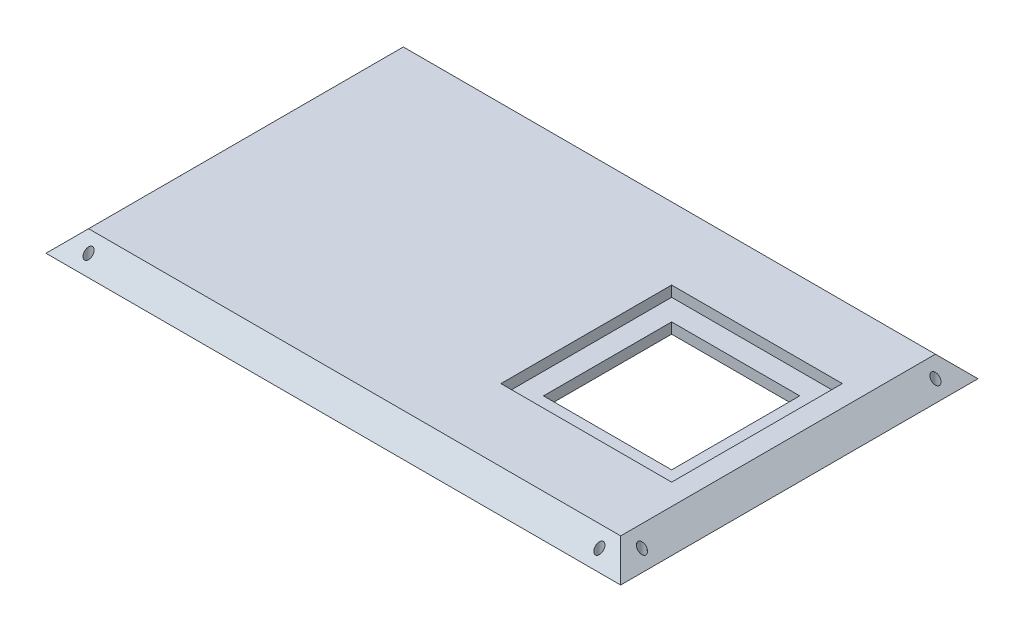
SolidWorks part; units mm, degrees
note: The reader was unsure of these and kept them because the rebuilt part matched: shared geometry of "Эскиз6<3>".
ref_plane "Спереди" through (0, 0, 0) normal (0, 0, 1) x (1, 0, 0)
ref_plane "Сверху" through (0, 0, 0) normal (0, 1, 0) x (1, 0, 0)
ref_plane "Справа" through (0, 0, 0) normal (1, 0, 0) x (0, 0, -1)
sketch "Эскиз1" plane through (0, 0, 0) normal (0, 1, 0) x (1, 0, 0)
  line L1 (-134.9958, -83.9404) -> (134.9958, -83.9404)
  line L2 (-134.9958, -83.9404) -> (-134.9958, 83.9404)
  line L3 (-134.9958, 83.9404) -> (134.9958, 83.9404)
  line L4 (134.9958, -83.9404) -> (134.9958, 83.9404)
  line L5 (-134.9958, -83.9404) -> (134.9958, 83.9404) construction
  line L6 (-134.9958, 83.9404) -> (134.9958, -83.9404) construction
  point P0 (0, 0)
  point P5 (134.9958, 83.9404)
ref_plane "Плоскость1" through (0, 10, 0) normal (0, 1, 0) x (1, 0, 0)
sketch "Эскиз2" plane through (0, 10, 0) normal (0, 1, 0) x (1, 0, 0)
  line L14 (-124.9958, 73.9404) -> (-124.9958, -73.9404)
  line L15 (-124.9958, -73.9404) -> (124.9958, -73.9404)
  line L16 (124.9958, -73.9404) -> (124.9958, 73.9404)
  line L17 (124.9958, 73.9404) -> (-124.9958, 73.9404)
  line L18 (-124.9958, 73.9404) -> (-124.9958, -73.9404)
  line L19 (-124.9958, -73.9404) -> (124.9958, -73.9404)
  line L20 (124.9958, -73.9404) -> (124.9958, 73.9404)
  line L21 (124.9958, 73.9404) -> (-124.9958, 73.9404)
  dimension "D1" = 10
loft "По сечениям1" add profiles "Эскиз1", "Эскиз2" connector at (134.9958, 0, 83.9404) connector at (124.9958, 10, 73.9404)
sketch "Эскиз3" plane through (0, 0, 0) normal (0, -1, 0) x (1, 0, 0)
  line L0 (-124.9958, -73.9404) -> (-124.9958, 73.9404) construction
  line L1 (-124.9958, 73.9404) -> (124.9958, 73.9404) construction
  line L2 (124.9958, 73.9404) -> (124.9958, -73.9404) construction
  line L3 (124.9958, -73.9404) -> (-124.9958, -73.9404) construction
  line L4 (-124.9958, -73.9404) -> (-124.9958, 73.9404) construction
  line L5 (-124.9958, 73.9404) -> (124.9958, 73.9404) construction
  line L6 (124.9958, 73.9404) -> (124.9958, -73.9404) construction
  line L7 (124.9958, -73.9404) -> (-124.9958, -73.9404) construction
  line L8 (-134.9958, 83.9404) -> (-124.9958, 73.9404) construction
  line L9 (-119.9958, 78.9404) -> (-119.9958, 83.9404) construction
  line L10 (-134.9958, 83.9404) -> (134.9958, 83.9404) construction
  line L11 (-119.9958, 78.9404) -> (-119.9958, 73.9404) construction
  line L12 (-124.9958, 73.9404) -> (-124.9958, 83.9404) construction
  line L13 (-124.9958, 78.9404) -> (-119.9958, 78.9404) construction
  line L14 (-119.9958, 78.9404) -> (-114.9958, 78.9404) construction
  line L15 (-114.9958, 78.9404) -> (-114.9958, 73.9404) construction
  line L16 (0, 83.9404) -> (0, -83.9404) construction
  line L17 (134.9958, -83.9404) -> (-134.9958, -83.9404) construction
  line L18 (-134.9958, 0) -> (134.9958, 0) construction
  line L19 (-134.9958, -83.9404) -> (-134.9958, 83.9404) construction
  line L20 (134.9958, 83.9404) -> (134.9958, -83.9404) construction
  circle A0 centre (-119.9958, 78.9404) radius 1.85
  circle A1 centre (-129.9958, 68.9404) radius 1.85
  circle A2 centre (129.9958, 68.9404) radius 1.85
  circle A3 centre (119.9958, 78.9404) radius 1.85
  circle A4 centre (129.9958, -68.9404) radius 1.85
  circle A5 centre (119.9958, -78.9404) radius 1.85
  circle A6 centre (-129.9958, -68.9404) radius 1.85
  circle A7 centre (-119.9958, -78.9404) radius 1.85
  dimension "D1" = 3.7
  dimension "D2" = 10
extrude "Вырез-Вытянуть1" cut sketch "Эскиз3" against normal through all
sketch "Эскиз4" plane through (0, 10, 0) normal (0, 1, 0) x (1, 0, 0)
  line L0 (-124.9958, 0) -> (124.9958, 0) construction
  line L1 (115.0958, -40.1) -> (34.8958, -40.1)
  line L2 (115.0958, -40.1) -> (115.0958, 40.1)
  line L3 (115.0958, 40.1) -> (34.8958, 40.1)
  line L4 (34.8958, -40.1) -> (34.8958, 40.1)
  line L5 (115.0958, -40.1) -> (34.8958, 40.1) construction
  line L6 (115.0958, 40.1) -> (34.8958, -40.1) construction
  line L7 (-124.9958, 73.9404) -> (-124.9958, -73.9404) construction
  line L8 (124.9958, -73.9404) -> (124.9958, 73.9404) construction
  point P0 (74.9958, 0)
  point P11 (0, 0)
  point P12 (74.9958, -40.1)
  dimension "D1" = 80.2
  dimension "D2" = 50
ref_plane "Плоскость2" through (0, 5, 0) normal (0, 1, 0) x (1, 0, 0)
sketch "Эскиз6" plane through (0, 5, 0) normal (0, 1, 0) x (1, 0, 0)
  line L0 (115.0958, 40.1) -> (34.8958, 40.1) construction
  line L1 (34.8958, -40.1) -> (34.8958, 40.1) construction
  line L2 (115.0958, -40.1) -> (115.0958, 40.1) construction
  line L3 (115.0958, -40.1) -> (34.8958, -40.1) construction
  line L4 (115.0958, 40.1) -> (34.8958, 40.1)
  line L5 (34.8958, -40.1) -> (34.8958, 40.1)
  line L6 (115.0958, -40.1) -> (115.0958, 40.1)
  line L7 (115.0958, -40.1) -> (34.8958, -40.1)
  line L8 (105.0958, -30.1) -> (44.8958, -30.1)
  line L9 (44.8958, -30.1) -> (44.8958, 30.1)
  line L10 (105.0958, 30.1) -> (44.8958, 30.1)
  line L11 (105.0958, -30.1) -> (105.0958, 30.1)
  dimension "D1" = 10
sketch "Эскиз7" plane through (0, 0, 0) normal (0, 1, 0) x (1, 0, 0)
  line L0 (105.0958, -30.1) -> (105.0958, 30.1) construction
  line L1 (105.0958, 30.1) -> (44.8958, 30.1) construction
  line L2 (44.8958, -30.1) -> (44.8958, 30.1) construction
  line L3 (105.0958, -30.1) -> (44.8958, -30.1) construction
  line L4 (105.0958, -30.1) -> (105.0958, 30.1)
  line L5 (105.0958, 30.1) -> (44.8958, 30.1)
  line L6 (44.8958, -30.1) -> (44.8958, 30.1)
  line L7 (105.0958, -30.1) -> (44.8958, -30.1)
loft "Вырез-По сечениям1" cut profiles "Эскиз7" section "Эскиз7" section "Эскиз6" connector at (44.8958, 0, 30.1) connector at (44.8958, 5, 30.1)
loft "Вырез-По сечениям2" cut profiles "Эскиз4" section "Эскиз6<3>" section "Эскиз4" connector at (34.8958, 5, 40.1) connector at (34.8958, 10, 40.1)
sketch "Эскиз6<3>" plane through (0, 5, 0) normal (0, 1, 0) x (1, 0, 0) same geometry as "Эскиз6"
